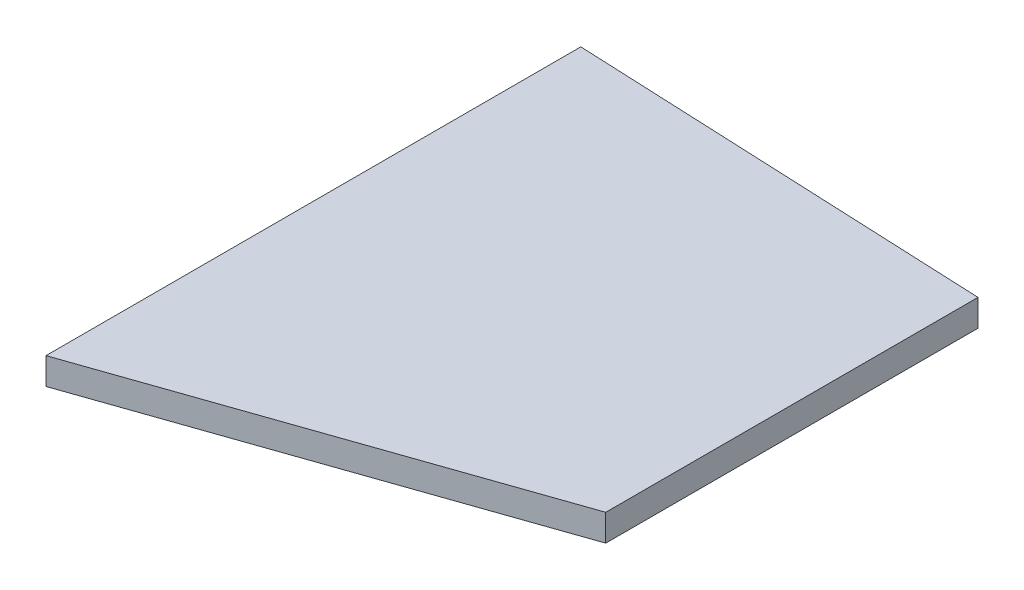
SolidWorks part; units mm, degrees
ref_plane "Front Plane" through (0, 0, 0) normal (0, 0, 1) x (1, 0, 0)
ref_plane "Top Plane" through (0, 0, 0) normal (0, 1, 0) x (1, 0, 0)
ref_plane "Right Plane" through (0, 0, 0) normal (1, 0, 0) x (0, 0, -1)
sketch "Sketch1" plane through (0, 0, 0) normal (0, 1, 0) x (1, 0, 0)
  line L1 (107.95, 0) -> (196.7632, 30.8151)
  line L3 (107.95, 114.3) -> (196.7632, 110.3723)
  line L4 (196.7632, 110.3723) -> (196.7632, 30.8151)
  line L5 (107.95, 114.3) -> (107.95, 0)
  line L7 (107.95, 114.3) -> (107.95, 0)
  line L9 (107.95, 104.1138) -> (107.95, 91.6704)
  line L13 (107.95, 79.8159) -> (107.95, 67.9614)
  line L17 (107.95, 54.217) -> (107.95, 43.737)
  line L21 (107.95, 28.2745) -> (107.95, 16.7636)
  dimension "D2" = 88.9
  dimension "D3" = 114.3
extrude "Boss-Extrude1" add sketch "Sketch1" along normal blind 5.715 contours L7 | L3 L7 L1 L4 region at (149.7038, 0, -63.4703)
